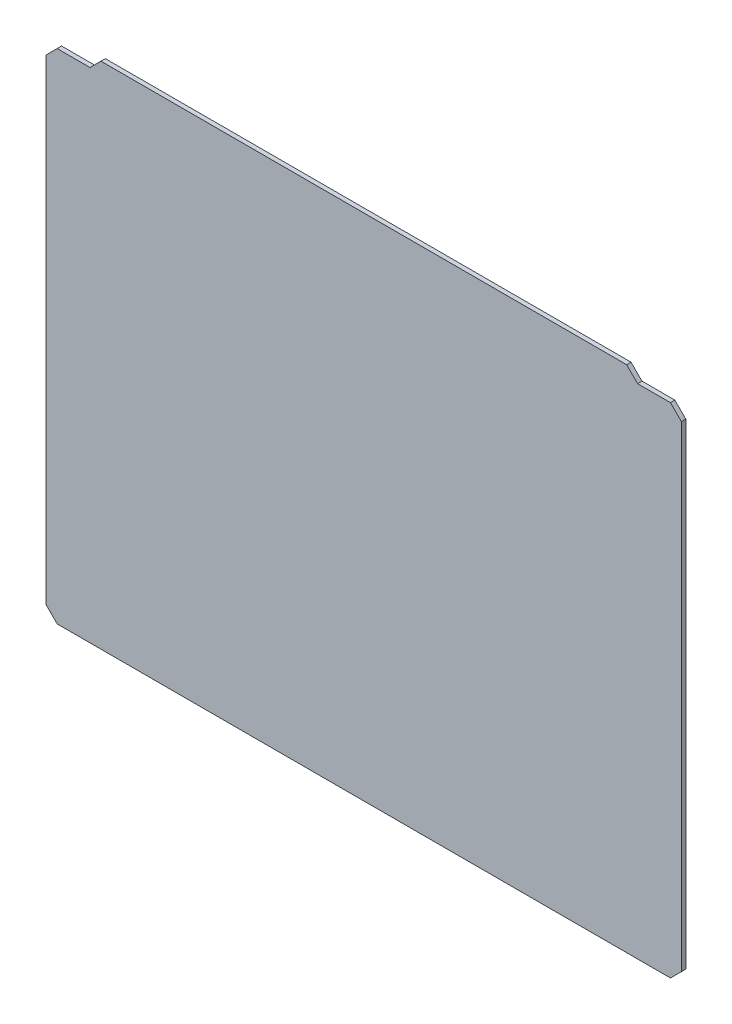
SolidWorks part; units mm, degrees
ref_plane "Front Plane" through (0, 0, 0) normal (0, 0, 1) x (1, 0, 0)
ref_plane "Top Plane" through (0, 0, 0) normal (0, 1, 0) x (1, 0, 0)
ref_plane "Right Plane" through (0, 0, 0) normal (1, 0, 0) x (0, 0, -1)
sketch "Sketch1" plane through (0, 0, 0) normal (0, 0, 1) x (1, 0, 0)
  line L0 (-41, -5) -> (-1, -5)
  line L1 (-1, 5) -> (-1, -5)
  line L2 (499, 5) -> (499, -5)
  line L4 (499, -5) -> (539, -5)
  line L5 (-41, -420) -> (-41, -460)
  line L6 (539, -5) -> (539, -420)
  line L7 (-1, 5) -> (499, 5)
  line L8 (1, -460) -> (497, -460)
  line L11 (-41, -460) -> (1, -460)
  line L12 (-41, -420) -> (-41, -5)
  line L13 (497, -460) -> (539, -460)
  line L15 (539, -460) -> (539, -420)
  dimension "D1" = 415
  dimension "D2" = 10
  dimension "D3" = 580
  dimension "D4" = 40
extrude "Boss-Extrude1" add sketch "Sketch1" along normal blind 4
chamfer "Chamfer1" distance 10 angle 45 2 edges at (499, 5, 2) (-1, 5, 2)
chamfer "Chamfer2" distance 10 angle 45 4 edges at (-41, -5, 2) (-41, -460, 2) (539, -460, 2) (539, -5, 2)
